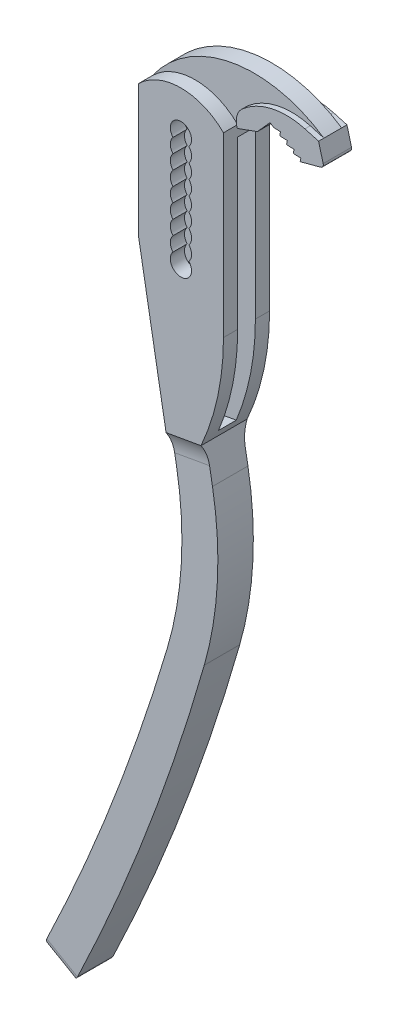
SolidWorks part; units mm, degrees
ref_plane "Front Plane" through (0, 0, 0) normal (0, 0, 1) x (1, 0, 0)
ref_plane "Top Plane" through (0, 0, 0) normal (0, 1, 0) x (1, 0, 0)
ref_plane "Right Plane" through (0, 0, 0) normal (1, 0, 0) x (0, 0, -1)
sketch "Sketch1" plane through (0, 0, 0) normal (0, 0, 1) x (1, 0, 0)
  line L0 (0, 0) -> (0, 84.5926) construction
  line L1 (-12, 24) -> (12, 24) construction
  line L2 (12, 24) -> (12, -26)
  line L3 (5.6622, -55.5799) -> (-4.1858, -57.3163)
  line L4 (-12, 24) -> (-12, -13)
  line L5 (-12, -13) -> (-4.1858, -57.3163)
  line L6 (0, 17.76) -> (0, 13.76) construction
  arc A0 (-12, 24) -> (12, 24) centre (0, 11.9584) cw
  arc A2 (12, -26) -> (5.6622, -55.5799) centre (-60.1972, -26) cw
  arc A3 (2.2361, 15.76) -> (-2.2361, 15.76) centre (0, 17.76) ccw
  arc A4 (2.2361, 11.76) -> (2.2361, 15.76) centre (0, 13.76) ccw
  arc A5 (-2.2361, 11.76) -> (-2.2361, 7.76) centre (0, 9.76) ccw
  arc A6 (-2.2361, 7.76) -> (-2.2361, 3.76) centre (0, 5.76) ccw
  arc A7 (2.2361, -0.24) -> (2.2361, 3.76) centre (0, 1.76) ccw
  arc A8 (2.2361, -4.24) -> (2.2361, -0.24) centre (0, -2.24) ccw
  arc A9 (-2.2361, -4.24) -> (-2.2361, -8.24) centre (0, -6.24) ccw
  arc A10 (-2.2361, -8.24) -> (-2.2361, -12.24) centre (0, -10.24) ccw
  arc A11 (-2.2361, -12.24) -> (2.2361, -12.24) centre (0, -14.24) ccw
  arc A12 (-2.2361, 15.76) -> (-2.2361, 11.76) centre (0, 13.76) ccw
  arc A13 (2.2361, 7.76) -> (2.2361, 11.76) centre (0, 9.76) ccw
  arc A14 (-2.2361, 3.76) -> (-2.2361, -0.24) centre (0, 1.76) ccw
  arc A15 (-2.2361, -0.24) -> (-2.2361, -4.24) centre (0, -2.24) ccw
  arc A16 (2.2361, -8.24) -> (2.2361, -4.24) centre (0, -6.24) ccw
  arc A17 (2.2361, -12.24) -> (2.2361, -8.24) centre (0, -10.24) ccw
  arc A18 (2.2361, 3.76) -> (2.2361, 7.76) centre (0, 5.76) ccw
  point P5 (0, 24)
  dimension "D3" = 17
  dimension "D8" = 10
  dimension "D9" = 6
  dimension "D1" = 24
  dimension "D2" = 24
  dimension "D4" = 50
  dimension "D5" = 37
  dimension "D6" = 45
  dimension "D7" = 10
  dimension "D10" = 17.76
  dimension "D11" = 4
  dimension "D12" = 9
extrude "Boss-Extrude1" add sketch "Sketch1" along normal mid plane 13
sketch "Sketch2" plane through (0, 0, 0) normal (0, 0, 1) x (1, 0, 0)
  line L0 (-4.1858, -57.3163) -> (-2.7413, -65.5089)
  line L1 (5.6622, -55.5799) -> (7.3987, -65.4279)
  line L2 (-40.1978, -201.0497) -> (-31.5376, -206.0497)
  line L3 (-4.1858, -57.3163) -> (5.6622, -55.5799)
  arc A0 (7.3987, -65.4279) -> (5.0786, -110.2358) centre (-91.082, -82.7928) cw
  arc A1 (-2.7413, -65.5089) -> (-5.3633, -111.3537) centre (-101.222, -82.8737) cw
  arc A2 (-5.3633, -111.3537) -> (-40.1978, -201.0497) centre (-570.9297, 56.6783) cw
  arc A3 (5.0786, -110.2358) -> (-31.5376, -206.0497) centre (-562.2694, 51.6783) cw
  dimension "D1" = 590
  dimension "D2" = 100
  dimension "D7" = 10
  dimension "D3" = 40
  dimension "D4" = 155
  dimension "D5" = 10
  dimension "D6" = 10
  dimension "D8" = 10.14
extrude "Boss-Extrude2" add sketch "Sketch2" along normal mid plane 10
sketch "Sketch3" plane through (0, 0, 0) normal (0, 0, 1) x (1, 0, 0)
  line L0 (12, 24) -> (19.0477, 26.5652)
  line L1 (19.0477, 26.5652) -> (22.627, 30.5414)
  line L2 (22.627, 30.5414) -> (31.1082, 25.2433)
  line L3 (31.1082, 25.2433) -> (36.9037, 26.7962)
  line L4 (37.6109, 28.0209) -> (36.3168, 32.8506)
  line L5 (19.0477, 26.5652) -> (47.5752, 36.9483) construction
  line L6 (12, -26) -> (12, 24) construction
  arc A0 (36.3168, 32.8506) -> (-12, 24) centre (16.6513, 3.8977) ccw
  arc A1 (12, 24) -> (-12, 24) centre (0, 11.9584) ccw construction
  arc A2 (12, 24) -> (-12, 24) centre (0, 11.9584) ccw
  arc A3 (36.9037, 26.7962) -> (37.6109, 28.0209) centre (36.6449, 27.7621) ccw
  point P15 (37.8697, 27.055)
  dimension "D1" = 110
  dimension "D9" = 35
  dimension "D10" = 1
  dimension "D2" = 7.5
  dimension "D3" = 5.35
  dimension "D4" = 10
  dimension "D5" = 100
  dimension "D6" = 7
  dimension "D7" = 6
  dimension "D8" = 5
extrude "Boss-Extrude3" add sketch "Sketch3" along normal mid plane 5
sketch "Sketch4" plane through (0, 0, 2.5) normal (0, 0, 1) x (1, 0, 0)
  line L0 (31.1082, 25.2433) -> (31.316, 26.2215)
  line L1 (31.316, 26.2215) -> (29.4377, 26.2868)
  line L2 (22.627, 30.5414) -> (31.1082, 25.2433) construction
  line L3 (29.4377, 26.2868) -> (31.1082, 25.2433)
  dimension "D1" = 1
  dimension "D2" = 70
  dimension "D3" = 80
extrude "Cut-Extrude1" cut sketch "Sketch4" against normal through all
pattern_linear "LPattern1" count 4 spacing 2.25 along (-0.8481, 0.5298, 0) of "Cut-Extrude1"
sketch "Sketch5" plane through (0, 0, 0) normal (0, 0, 1) x (1, 0, 0)
  line L2 (12, 24) -> (19.0477, 26.5652) construction
  line L4 (13.4095, 24.513) -> (19.0477, 26.5652)
  line L5 (36.3168, 32.8506) -> (32.4679, 33.9399)
  line L17 (27.5295, 27.4789) -> (29.4077, 27.4135)
  line L18 (29.4077, 27.4135) -> (29.1999, 26.4354)
  line L19 (29.1999, 26.4354) -> (29.4377, 26.2868)
  line L20 (29.4377, 26.2868) -> (31.316, 26.2215)
  line L21 (31.316, 26.2215) -> (31.1082, 25.2433)
  line L22 (31.1082, 25.2433) -> (36.9037, 26.7962)
  line L23 (37.6109, 28.0209) -> (36.3168, 32.8506)
  line L24 (12, 24) -> (19.0477, 26.5652)
  line L25 (19.0477, 26.5652) -> (22.627, 30.5414)
  line L26 (22.627, 30.5414) -> (23.713, 29.8631)
  line L27 (23.713, 29.8631) -> (25.5912, 29.7977)
  line L28 (25.5912, 29.7977) -> (25.3834, 28.8195)
  line L29 (25.3834, 28.8195) -> (25.6212, 28.671)
  line L30 (25.6212, 28.671) -> (27.4995, 28.6056)
  line L31 (27.4995, 28.6056) -> (27.2917, 27.6274)
  line L32 (27.2917, 27.6274) -> (27.5295, 27.4789)
  line L33 (27.5295, 27.4789) -> (29.4077, 27.4135)
  line L34 (29.4077, 27.4135) -> (29.1999, 26.4354)
  line L35 (29.1999, 26.4354) -> (29.4377, 26.2868)
  line L36 (29.4377, 26.2868) -> (31.316, 26.2215)
  line L37 (31.316, 26.2215) -> (31.1082, 25.2433)
  line L38 (31.1082, 25.2433) -> (36.9037, 26.7962)
  line L39 (37.6109, 28.0209) -> (36.3168, 32.8506)
  line L41 (19.0477, 26.5652) -> (22.627, 30.5414)
  line L42 (22.627, 30.5414) -> (23.713, 29.8631)
  line L43 (23.713, 29.8631) -> (25.5912, 29.7977)
  line L44 (25.5912, 29.7977) -> (25.3834, 28.8195)
  line L45 (25.3834, 28.8195) -> (25.6212, 28.671)
  line L46 (25.6212, 28.671) -> (27.4995, 28.6056)
  line L47 (27.4995, 28.6056) -> (27.2917, 27.6274)
  line L48 (27.2917, 27.6274) -> (27.5295, 27.4789)
  arc A3 (32.4679, 33.9399) -> (14.8274, 29.9964) centre (27.2937, 15.658) ccw
  arc A4 (36.9037, 26.7962) -> (37.6109, 28.0209) centre (36.6449, 27.7621) ccw
  arc A5 (36.3168, 32.8506) -> (-12, 24) centre (16.6513, 3.8977) ccw
  arc A6 (12, 24) -> (-12, 24) centre (0, 11.9584) ccw
  arc A7 (36.9037, 26.7962) -> (37.6109, 28.0209) centre (36.6449, 27.7621) ccw
  arc A8 (14.8274, 29.9964) -> (13.4095, 24.513) centre (18.108, 26.2231) ccw
  point P4 (0, 0)
  point P18 (0, 0)
  point P21 (0, 0)
  point P23 (0, 0)
  dimension "D1" = 4
  dimension "D2" = 19
  dimension "D4" = 5
  dimension "D5" = 6
  dimension "D3" = 0
extrude "Boss-Extrude4" add sketch "Sketch5" along normal mid plane 8
fillet "Fillet1" radius 10 2 edges at (0.7382, -56.4481, 5) (0.7382, -56.4481, -5)
fillet "Fillet2" radius 2 4 edges at (-40.1978, -201.0497, 0) (-35.8677, -203.5497, 5) (-31.5376, -206.0497, 0) (-35.8677, -203.5497, -5)
sketch "Sketch10" plane through (0, 0, 0) normal (0, 0, 1) x (1, 0, 0)
  line L2 (-4.5331, -55.3467) -> (6.6057, -53.3827)
  line L3 (-12, -13) -> (-4.1858, -57.3163) construction
  line L4 (12, -26) -> (12, 24) construction
  line L5 (-12, 24) -> (-12, -13) construction
  line L6 (-12, -13) -> (-4.5331, -55.3467)
  line L7 (12, -26) -> (12, 20.9584)
  line L8 (-12, 20.9584) -> (-12, -13)
  line L9 (-4.1858, -57.3163) -> (5.6622, -55.5799) construction
  arc A2 (12, 20.9584) -> (-12, 20.9584) centre (0, 11.9584) ccw
  arc A3 (5.6622, -55.5799) -> (12, -26) centre (-60.1972, -26) ccw construction
  arc A4 (6.6057, -53.3827) -> (12, -26) centre (-60.1972, -26) ccw
  arc A5 (12, 24) -> (-12, 24) centre (0, 11.9584) ccw construction
  point P7 (0, 0)
  point P10 (0, 0)
  point P16 (0, 0)
  point P17 (0, 0)
  point P21 (0, 28.9584)
  point P22 (0, 0)
  point P23 (0, 0)
  point P24 (0, 26.9584)
  point P26 (0, 0)
  point P27 (0, 0)
  point P28 (0, 0)
  point P29 (0, 0)
  point P30 (0, 0)
  dimension "D3" = 15
  dimension "D1" = 2
  dimension "D2" = 2
extrude "Cut-Extrude4" cut sketch "Sketch10" against normal mid plane 5
